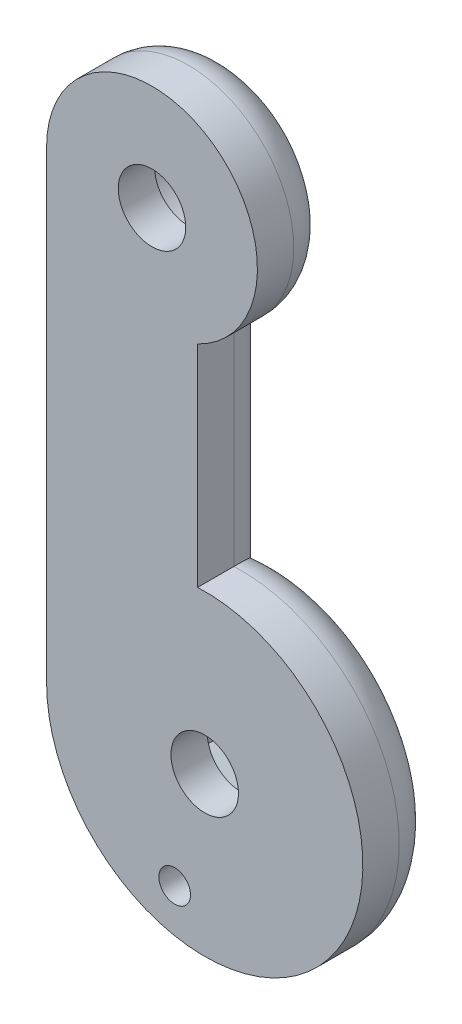
SolidWorks part; units mm, degrees
ref_plane "Front Plane" through (0, 0, 0) normal (0, 0, 1) x (1, 0, 0)
ref_plane "Top Plane" through (0, 0, 0) normal (0, 1, 0) x (1, 0, 0)
ref_plane "Right Plane" through (0, 0, 0) normal (1, 0, 0) x (0, 0, -1)
sketch "Sketch1" plane through (0, 0, 0) normal (0, 0, 1) x (1, 0, 0)
  line L0 (-7.5, 22) -> (-7.5, 0)
  line L2 (-0.3362, 7.4925) -> (-0.3362, 17.4925)
  circle A0 centre (0, 0) radius 1.6
  arc A1 (-7.5, 0) -> (-0.3362, 7.4925) centre (0, 0) ccw
  circle A2 centre (-2.5, 22) radius 1.6
  arc A3 (-0.3362, 17.4925) -> (-7.5, 22) centre (-2.5, 22) ccw
  dimension "D2" = 10
  dimension "D3" = 3.2
  dimension "D4" = 15
  dimension "D5" = 10
  dimension "D6" = 22
extrude "Boss-Extrude1" add sketch "Sketch1" along normal blind 3.6
sketch "Sketch2" plane through (0, 0, 3.6) normal (0, 0, 1) x (1, 0, 0)
  line L0 (0, 0) -> (-1.4235, -5.3126) construction
  line L2 (0, 0) -> (0, 1.6) construction
  circle A0 centre (-1.4235, -5.3126) radius 0.75
  circle A1 centre (0, 0) radius 1.6 construction
  dimension "D2" = 1.5
  dimension "D1" = 5.5
  dimension "D3" = 165
extrude "Cut-Extrude1" cut sketch "Sketch2" against normal through all
sketch "Sketch3" plane through (0, 0, 3.6) normal (0, 0, 1) x (1, 0, 0)
  line L1 (0, 3.2043) -> (-2.775, 1.6021)
  line L2 (-2.775, 1.6021) -> (-2.775, -1.6021)
  line L3 (-2.775, -1.6021) -> (0, -3.2043)
  line L4 (0, -3.2043) -> (2.775, -1.6021)
  line L5 (2.775, -1.6021) -> (2.775, 1.6021)
  line L6 (2.775, 1.6021) -> (0, 3.2043)
  line L7 (-2.5, 18.7957) -> (0.275, 20.3979)
  line L8 (0.275, 20.3979) -> (0.275, 23.6021)
  line L9 (0.275, 23.6021) -> (-2.5, 25.2043)
  line L10 (-2.5, 25.2043) -> (-5.275, 23.6021)
  line L11 (-5.275, 23.6021) -> (-5.275, 20.3979)
  line L12 (-5.275, 20.3979) -> (-2.5, 18.7957)
  circle A0 centre (0, 0) radius 2.775 construction
  circle A1 centre (-2.5, 22) radius 2.775 construction
  dimension "D1" = 5.55
extrude "Cut-Extrude2" [suppressed] cut sketch "Sketch3" against normal blind 1.875
sketch "Sketch4" plane through (0, 0, 0) normal (0, 0, -1) x (-1, 0, 0)
  line L1 (0, 3.1754) -> (-2.75, 1.5877)
  line L2 (-2.75, 1.5877) -> (-2.75, -1.5877)
  line L3 (-2.75, -1.5877) -> (0, -3.1754)
  line L4 (0, -3.1754) -> (2.75, -1.5877)
  line L5 (2.75, -1.5877) -> (2.75, 1.5877)
  line L6 (2.75, 1.5877) -> (0, 3.1754)
  circle A1 centre (2.5, 22) radius 2.775
  circle A2 centre (0, 0) radius 2.75 construction
  dimension "D1" = 5.55
  dimension "D2" = 5.5
extrude "Cut-Extrude3" cut sketch "Sketch4" against normal blind 1.875
fillet "Fillet1" [suppressed] radius 1.875
fillet "Fillet2" radius 1.875 4 edges at (0.1628, 26.232, 0) (5.4209, -5.1831, 0) (-0.3362, 12.4925, 0) (-7.5, 11, 0)
